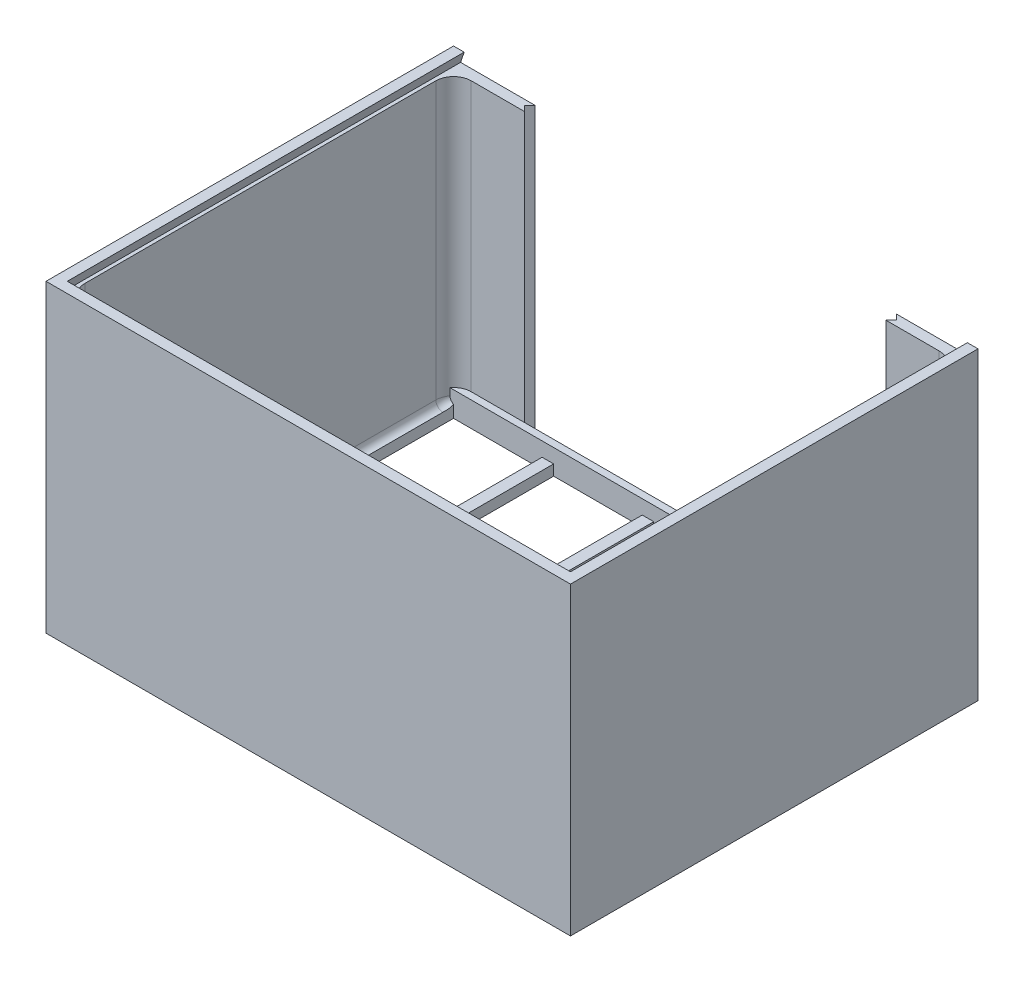
SolidWorks part; units mm, degrees
ref_plane "前视基准面" through (0, 0, 0) normal (0, 0, 1) x (1, 0, 0)
ref_plane "上视基准面" through (0, 0, 0) normal (0, 1, 0) x (1, 0, 0)
ref_plane "右视基准面" through (0, 0, 0) normal (1, 0, 0) x (0, 0, -1)
sketch "Sketch1" plane through (0, 0, 0) normal (0, 1, 0) x (1, 0, 0)
  line L0 (-5, -5) -> (143, -5)
  line L1 (0, 78) -> (0, 54)
  line L2 (0, 51) -> (0, 27)
  line L3 (28.25, 78) -> (28.25, 54)
  line L4 (28.25, 51) -> (28.25, 27)
  line L5 (143, -5) -> (143, 110)
  line L6 (-5, 110) -> (143, 110)
  line L7 (-5, -5) -> (-5, 110)
  line L8 (0, 24) -> (0, 0)
  line L9 (0, 105) -> (25, 105)
  line L10 (0, 105) -> (0, 81)
  line L11 (0, 81) -> (25, 81)
  line L12 (25, 105) -> (25, 81)
  line L13 (28.25, 24) -> (28.25, 0)
  line L14 (28.25, 105) -> (53.25, 105)
  line L15 (28.25, 105) -> (28.25, 81)
  line L16 (28.25, 81) -> (53.25, 81)
  line L17 (53.25, 105) -> (53.25, 81)
  line L18 (28.25, 78) -> (53.25, 78)
  line L19 (28.25, 54) -> (53.25, 54)
  line L20 (53.25, 78) -> (53.25, 54)
  line L21 (28.25, 51) -> (53.25, 51)
  line L22 (28.25, 27) -> (53.25, 27)
  line L23 (53.25, 51) -> (53.25, 27)
  line L24 (28.25, 24) -> (53.25, 24)
  line L25 (28.25, 0) -> (53.25, 0)
  line L26 (53.25, 24) -> (53.25, 0)
  line L27 (56.5, 78) -> (56.5, 54)
  line L28 (0, 78) -> (25, 78)
  line L29 (0, 54) -> (25, 54)
  line L30 (25, 78) -> (25, 54)
  line L31 (56.5, 51) -> (56.5, 27)
  line L32 (56.5, 24) -> (56.5, 0)
  line L33 (56.5, 105) -> (81.5, 105)
  line L34 (56.5, 105) -> (56.5, 81)
  line L35 (56.5, 81) -> (81.5, 81)
  line L36 (81.5, 105) -> (81.5, 81)
  line L37 (56.5, 78) -> (81.5, 78)
  line L38 (56.5, 54) -> (81.5, 54)
  line L39 (81.5, 78) -> (81.5, 54)
  line L40 (56.5, 51) -> (81.5, 51)
  line L41 (56.5, 27) -> (81.5, 27)
  line L42 (81.5, 51) -> (81.5, 27)
  line L43 (56.5, 24) -> (81.5, 24)
  line L44 (56.5, 0) -> (81.5, 0)
  line L45 (81.5, 24) -> (81.5, 0)
  line L46 (84.75, 78) -> (84.75, 54)
  line L47 (0, 51) -> (25, 51)
  line L48 (0, 27) -> (25, 27)
  line L49 (25, 51) -> (25, 27)
  line L50 (84.75, 51) -> (84.75, 27)
  line L51 (84.75, 24) -> (84.75, 0)
  line L52 (84.75, 105) -> (109.75, 105)
  line L53 (84.75, 105) -> (84.75, 81)
  line L54 (84.75, 81) -> (109.75, 81)
  line L55 (109.75, 105) -> (109.75, 81)
  line L56 (84.75, 78) -> (109.75, 78)
  line L57 (84.75, 54) -> (109.75, 54)
  line L58 (109.75, 78) -> (109.75, 54)
  line L59 (84.75, 51) -> (109.75, 51)
  line L60 (84.75, 27) -> (109.75, 27)
  line L61 (109.75, 51) -> (109.75, 27)
  line L62 (84.75, 24) -> (109.75, 24)
  line L63 (84.75, 0) -> (109.75, 0)
  line L64 (109.75, 24) -> (109.75, 0)
  line L65 (113, 78) -> (113, 54)
  line L66 (0, 24) -> (25, 24)
  line L67 (0, 0) -> (25, 0)
  line L68 (25, 24) -> (25, 0)
  line L69 (113, 51) -> (113, 27)
  line L70 (113, 24) -> (113, 0)
  line L71 (113, 105) -> (138, 105)
  line L72 (113, 105) -> (113, 81)
  line L73 (113, 81) -> (138, 81)
  line L74 (138, 105) -> (138, 81)
  line L75 (113, 78) -> (138, 78)
  line L76 (113, 54) -> (138, 54)
  line L77 (138, 78) -> (138, 54)
  line L78 (113, 51) -> (138, 51)
  line L79 (113, 27) -> (138, 27)
  line L80 (138, 51) -> (138, 27)
  line L81 (113, 24) -> (138, 24)
  line L82 (113, 0) -> (138, 0)
  line L83 (138, 24) -> (138, 0)
  dimension "D1" = 4
  dimension "D2" = 5
  dimension "D3" = 148
  dimension "D4" = 115
  dimension "D5" = 25
  dimension "D6" = 24
  dimension "D7" = 5
  dimension "D8" = 5
  dimension "D9" = 5
  dimension "D10" = 5
extrude "Boss-Extrude2" add sketch "Sketch1" along normal blind 3
sketch "Sketch4" plane through (0, 3, 0) normal (0, 1, 0) x (1, 0, 0)
  line L0 (143, 110) -> (-5, 110) construction
  line L1 (-5, -5) -> (143, -5)
  line L2 (-5, -5) -> (-5, 110)
  line L3 (-5, 110) -> (18, 110)
  line L4 (143, -5) -> (143, 110)
  line L5 (120, 110) -> (143, 110)
  line L6 (-2, 107) -> (18, 107)
  line L7 (18, 110) -> (16.5, 108.5)
  line L8 (-2, -2) -> (-2, 107)
  line L9 (69, 110) -> (69, -2) construction
  line L10 (140, -2) -> (140, 107)
  line L11 (-2, -2) -> (140, -2)
  line L12 (16.5, 108.5) -> (18, 107)
  line L13 (120, 107) -> (140, 107)
  line L14 (120, 110) -> (121.5, 108.5)
  line L15 (121.5, 108.5) -> (120, 107)
  dimension "D1" = 3
  dimension "D2" = 3
  dimension "D3" = 3
  dimension "D4" = 20
extrude "Boss-Extrude3" add sketch "Sketch4" along normal blind 80
sketch "Sketch21" plane through (0, 3, 0) normal (0, 1, 0) x (1, 0, 0)
  line L0 (53.25, 105) -> (28.25, 105) construction
  line L1 (-2, 105) -> (140, 105)
  line L2 (-2, 105) -> (-2, 107)
  line L3 (-2, 107) -> (140, 107)
  line L4 (140, 105) -> (140, 107)
  line L5 (-2, -2) -> (-2, 107) construction
  line L6 (140, 107) -> (140, -2) construction
extrude "Boss-Extrude9" add sketch "Sketch21" along normal blind 4
sketch "Sketch16" plane through (0, 3, 0) normal (0, 1, 0) x (1, 0, 0)
  line L0 (140, -2) -> (-2, -2) construction
  line L1 (-2, 105) -> (-2, -2) construction
  line L3 (-2, 40) -> (5.5, 40) construction
  line L4 (5.5, 42) -> (-2, 42)
  line L5 (-2, 42) -> (-2, 38)
  line L6 (-2, 38) -> (5.5, 38)
  line L7 (69, 110) -> (69, -2) construction
  line L9 (-2, -2) -> (140, -2) construction
  line L10 (140, 40) -> (132.5, 40) construction
  line L12 (140, 38) -> (132.5, 38)
  line L13 (140, 42) -> (140, 38)
  line L14 (132.5, 42) -> (140, 42)
  line L16 (120, 110) -> (18, 110) construction
  arc A0 (5.5, 38) -> (5.5, 42) centre (5.5, 40) ccw
  arc A1 (132.5, 38) -> (132.5, 42) centre (132.5, 40) cw
  point P2 (7.5, 40)
  dimension "D1" = 40
  dimension "D3" = 9.5
  dimension "D2" = 4
extrude "Boss-Extrude7" add sketch "Sketch16" along normal blind 8 and the other way blind 3
sketch "Sketch17" plane through (0, 83, 0) normal (0, 1, 0) x (1, 0, 0)
  line L1 (-2, 110) -> (-5, 110)
  line L2 (-5, 110) -> (-5, -5) construction
  line L3 (-5, 110) -> (-5, -5)
  line L4 (-5, -5) -> (143, -5)
  line L6 (143, -5) -> (143, 110)
  line L7 (143, -5) -> (143, 110) construction
  line L8 (143, 110) -> (140, 110)
  line L9 (140, 110) -> (140, -2)
  line L10 (140, -2) -> (-2, -2)
  line L11 (-2, -2) -> (-2, 110)
extrude "Boss-Extrude8" add sketch "Sketch17" along normal blind 3
sketch "Sketch18" plane through (0, 0, -110) normal (0, 0, -1) x (-1, 0, 0)
  line L0 (2, 86) -> (3, 83)
  line L1 (3, 83) -> (2, 83)
  line L2 (2, 86) -> (2, 3) construction
  line L3 (2, 83) -> (2, 86)
  line L4 (-69, 86) -> (-69, 0) construction
  line L5 (-140, 86) -> (2, 86) construction
  line L6 (-143, 0) -> (5, 0) construction
  line L7 (-140, 83) -> (-140, 86)
  line L8 (-141, 83) -> (-140, 83)
  line L9 (-140, 86) -> (-141, 83)
  dimension "D1" = 3
  dimension "D2" = 1
extrude "Cut-Extrude1" cut sketch "Sketch18" against normal up to surface (112 mm away) up to face at (69, 44.5, 2)
fillet "Fillet1" radius 5 4 edges at (140, 43, 2) (-2, 43, 2)
fillet "Fillet2" radius 2 9 edges at (139.7434, 3, -103.5811) (138.5355, 3, 0.5355) (-0.5355, 3, 0.5355) (-1.7434, 3, -103.5811) (140, 3, -72) (140, 3, -20.5) (69, 3, 2) (-2, 3, -20.5) (-2, 3, -72)
